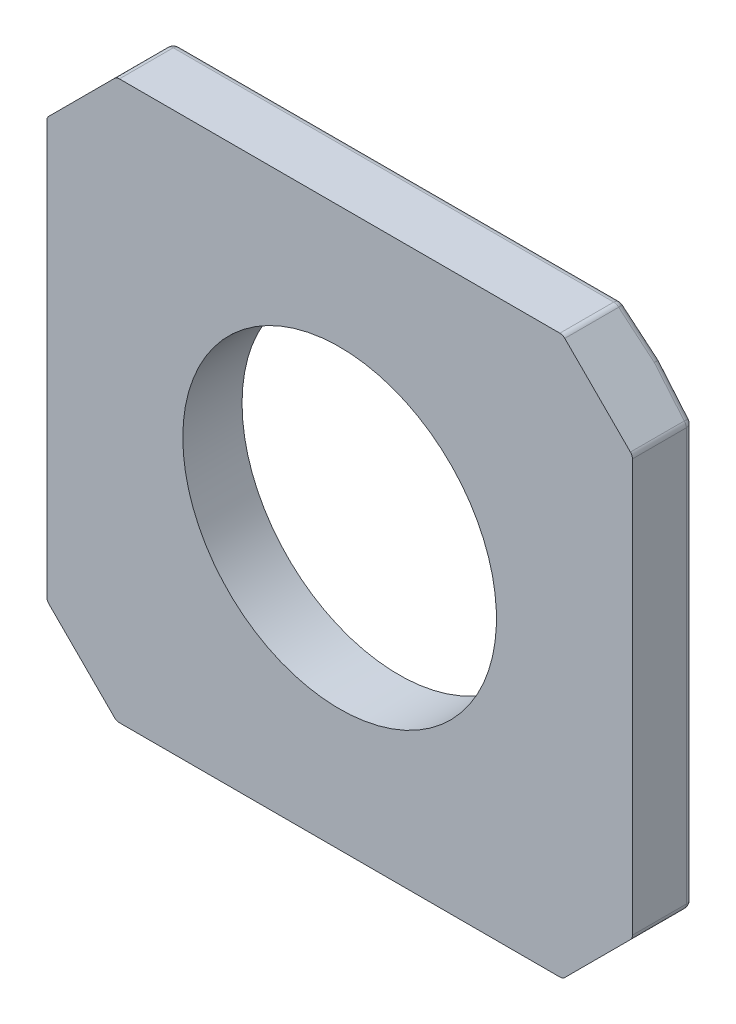
SolidWorks part; units mm, degrees
ref_plane "Top plane" through (0, 0, 0) normal (0, 0, 1) x (1, 0, 0)
ref_plane "Right plane" through (0, 0, 0) normal (0, 1, 0) x (1, 0, 0)
ref_plane "Front plane" through (0, 0, 0) normal (1, 0, 0) x (0, 0, -1)
sketch "Sketch1" plane through (0, 0, 0) normal (0, 0, 1) x (1, 0, 0)
  line L1 (-84.021, 80) -> (84.021, 80)
  line L2 (-84.021, 80) -> (-84.021, -80)
  line L3 (-84.021, -80) -> (84.021, -80)
  line L4 (84.021, 80) -> (84.021, -80)
  line L5 (-84.021, 80) -> (84.021, -80) construction
  line L6 (-60.2161, 15.1309) -> (-64.6493, 12.445)
  line L7 (-64.6493, -12.445) -> (-60.2161, -15.1309)
  line L8 (17.0043, -59.7141) -> (21.5469, -62.2104)
  line L9 (43.1024, -49.7654) -> (43.2118, -44.5833)
  line L10 (43.2118, 44.5833) -> (43.1024, 49.7654)
  line L11 (21.5469, 62.2104) -> (17.0043, 59.7141)
  line L18 (-84.021, -80) -> (84.021, 80) construction
  arc A18 (13.5845, 59.2373) -> (-58.0933, 17.8542) centre (0, 0) ccw
  arc A19 (-60.2161, 15.1309) -> (-58.0933, 17.8542) centre (-62.7293, 19.279) ccw
  arc A20 (-64.6493, 12.445) -> (-67.0879, 8.7029) centre (-61.9807, 8.0404) ccw
  arc A21 (-67.0879, 8.7029) -> (-67.0879, -8.7029) centre (0, 0) ccw
  arc A22 (-67.0879, -8.7029) -> (-64.6493, -12.445) centre (-61.9807, -8.0404) ccw
  arc A23 (-58.0933, -17.8542) -> (-60.2161, -15.1309) centre (-62.7293, -19.279) ccw
  arc A24 (-58.0933, -17.8542) -> (13.5845, -59.2373) centre (0, 0) ccw
  arc A25 (17.0043, -59.7141) -> (13.5845, -59.2373) centre (14.6686, -63.9646) ccw
  arc A26 (21.5469, -62.2104) -> (26.007, -62.4512) centre (24.0272, -57.697) ccw
  arc A27 (26.007, -62.4512) -> (41.0809, -53.7483) centre (0, 0) ccw
  arc A28 (41.0809, -53.7483) -> (43.1024, -49.7654) centre (37.9535, -49.6566) ccw
  arc A29 (44.5088, -41.3832) -> (43.2118, -44.5833) centre (48.0607, -44.6857) ccw
  arc A30 (44.5088, -41.3832) -> (44.5088, 41.3832) centre (0, 0) ccw
  arc A31 (43.2118, 44.5833) -> (44.5088, 41.3832) centre (48.0607, 44.6857) ccw
  arc A32 (43.1024, 49.7654) -> (41.0809, 53.7483) centre (37.9535, 49.6566) ccw
  arc A33 (41.0809, 53.7483) -> (26.007, 62.4512) centre (0, 0) ccw
  arc A34 (26.007, 62.4512) -> (21.5469, 62.2104) centre (24.0272, 57.697) ccw
  arc A35 (13.5845, 59.2373) -> (17.0043, 59.7141) centre (14.6686, 63.9646) ccw
  dimension "D2" = 60.775
  dimension "D3" = 4.85
  dimension "D4" = 160
  dimension "D5" = 60.775
  dimension "D6" = 67.65
  dimension "D1" = 90
  dimension "D7" = 17.4058
extrude "Boss-Extrude1" add sketch "Sketch1" against normal blind 3 contours L4 L1 L2 L3 A18 A35 L11 A34 A33 A32 L10 A31 A30 A29 L9 A28 A27 A26 L8 A25 A24 A23 L7 A22 A21 A20 L6 A19 region at (0, 77.6797, 0)
sketch "Sketch3" plane through (0, 0, 0) normal (0, 0, 1) x (1, 0, 0)
  line L4 (84.021, -80) -> (84.021, 80)
  line L5 (84.021, 80) -> (-84.021, 80)
  line L6 (-84.021, 80) -> (-84.021, -80)
  line L7 (-84.021, -80) -> (84.021, -80)
  line L8 (84.021, -80) -> (84.021, 80)
  line L9 (84.021, 80) -> (-84.021, 80)
  line L10 (-84.021, 80) -> (-84.021, -80)
  line L11 (-84.021, -80) -> (84.021, -80)
  line L12 (84.021, 80) -> (-84.021, 80)
  line L13 (84.021, -80) -> (84.021, 80)
  line L14 (-84.021, -80) -> (84.021, -80)
  line L15 (-84.021, 80) -> (-84.021, -80)
  line L16 (84.021, 80) -> (-84.021, 80)
  line L17 (84.021, -80) -> (84.021, 80)
  line L18 (-84.021, -80) -> (84.021, -80)
  line L19 (-84.021, 80) -> (-84.021, -80)
  line L22 (21.5469, 62.2104) -> (17.0043, 59.7141)
  line L23 (-60.2161, 15.1309) -> (-64.6493, 12.445)
  line L24 (-64.6493, -12.445) -> (-60.2161, -15.1309)
  line L25 (17.0043, -59.7141) -> (21.5469, -62.2104)
  line L26 (43.1024, -49.7654) -> (43.2118, -44.5833)
  line L27 (43.2118, 44.5833) -> (43.1024, 49.7654)
  line L28 (21.5469, 62.2104) -> (17.0043, 59.7141)
  line L29 (-60.2161, 15.1309) -> (-64.6493, 12.445)
  line L30 (-64.6493, -12.445) -> (-60.2161, -15.1309)
  line L31 (17.0043, -59.7141) -> (21.5469, -62.2104)
  line L32 (43.1024, -49.7654) -> (43.2118, -44.5833)
  line L33 (43.2118, 44.5833) -> (43.1024, 49.7654)
  circle A0 centre (0, 0) radius 45
  arc A18 (13.5845, 59.2373) -> (17.0043, 59.7141) centre (14.6686, 63.9646) ccw
  arc A19 (13.5845, 59.2373) -> (-58.0933, 17.8542) centre (0, 0) ccw
  arc A20 (-60.2161, 15.1309) -> (-58.0933, 17.8542) centre (-62.7293, 19.279) ccw
  arc A21 (-64.6493, 12.445) -> (-67.0879, 8.7029) centre (-61.9807, 8.0404) ccw
  arc A22 (-67.0879, 8.7029) -> (-67.0879, -8.7029) centre (0, 0) ccw
  arc A23 (-67.0879, -8.7029) -> (-64.6493, -12.445) centre (-61.9807, -8.0404) ccw
  arc A24 (-58.0933, -17.8542) -> (-60.2161, -15.1309) centre (-62.7293, -19.279) ccw
  arc A25 (-58.0933, -17.8542) -> (13.5845, -59.2373) centre (0, 0) ccw
  arc A26 (17.0043, -59.7141) -> (13.5845, -59.2373) centre (14.6686, -63.9646) ccw
  arc A27 (21.5469, -62.2104) -> (26.007, -62.4512) centre (24.0272, -57.697) ccw
  arc A28 (26.007, -62.4512) -> (41.0809, -53.7483) centre (0, 0) ccw
  arc A29 (41.0809, -53.7483) -> (43.1024, -49.7654) centre (37.9535, -49.6566) ccw
  arc A30 (44.5088, -41.3832) -> (43.2118, -44.5833) centre (48.0607, -44.6857) ccw
  arc A31 (44.5088, -41.3832) -> (44.5088, 41.3832) centre (0, 0) ccw
  arc A32 (43.2118, 44.5833) -> (44.5088, 41.3832) centre (48.0607, 44.6857) ccw
  arc A33 (43.1024, 49.7654) -> (41.0809, 53.7483) centre (37.9535, 49.6566) ccw
  arc A34 (41.0809, 53.7483) -> (26.007, 62.4512) centre (0, 0) ccw
  arc A35 (26.007, 62.4512) -> (21.5469, 62.2104) centre (24.0272, 57.697) ccw
  arc A36 (13.5845, 59.2373) -> (17.0043, 59.7141) centre (14.6686, 63.9646) ccw
  arc A37 (13.5845, 59.2373) -> (-58.0933, 17.8542) centre (0, 0) ccw
  arc A38 (-60.2161, 15.1309) -> (-58.0933, 17.8542) centre (-62.7293, 19.279) ccw
  arc A39 (-64.6493, 12.445) -> (-67.0879, 8.7029) centre (-61.9807, 8.0404) ccw
  arc A40 (-67.0879, 8.7029) -> (-67.0879, -8.7029) centre (0, 0) ccw
  arc A41 (-67.0879, -8.7029) -> (-64.6493, -12.445) centre (-61.9807, -8.0404) ccw
  arc A42 (-58.0933, -17.8542) -> (-60.2161, -15.1309) centre (-62.7293, -19.279) ccw
  arc A43 (-58.0933, -17.8542) -> (13.5845, -59.2373) centre (0, 0) ccw
  arc A44 (17.0043, -59.7141) -> (13.5845, -59.2373) centre (14.6686, -63.9646) ccw
  arc A45 (21.5469, -62.2104) -> (26.007, -62.4512) centre (24.0272, -57.697) ccw
  arc A46 (26.007, -62.4512) -> (41.0809, -53.7483) centre (0, 0) ccw
  arc A47 (41.0809, -53.7483) -> (43.1024, -49.7654) centre (37.9535, -49.6566) ccw
  arc A48 (44.5088, -41.3832) -> (43.2118, -44.5833) centre (48.0607, -44.6857) ccw
  arc A49 (44.5088, -41.3832) -> (44.5088, 41.3832) centre (0, 0) ccw
  arc A50 (43.2118, 44.5833) -> (44.5088, 41.3832) centre (48.0607, 44.6857) ccw
  arc A51 (43.1024, 49.7654) -> (41.0809, 53.7483) centre (37.9535, 49.6566) ccw
  arc A52 (41.0809, 53.7483) -> (26.007, 62.4512) centre (0, 0) ccw
  arc A53 (26.007, 62.4512) -> (21.5469, 62.2104) centre (24.0272, 57.697) ccw
  arc M37 (-58.0933, 17.8542) -> (13.5845, 59.2373) centre (0, 0) cw
  arc M38 (13.5845, 59.2373) -> (17.0043, 59.7141) centre (14.6686, 63.9646) ccw
  line M39 (17.0043, 59.7141) -> (21.5469, 62.2104)
  arc M40 (21.5469, 62.2104) -> (26.007, 62.4512) centre (24.0272, 57.697) cw
  arc M41 (26.007, 62.4512) -> (41.0809, 53.7483) centre (0, 0) cw
  arc M42 (41.0809, 53.7483) -> (43.1024, 49.7654) centre (37.9535, 49.6566) cw
  line M43 (43.1024, 49.7654) -> (43.2118, 44.5833)
  arc M44 (43.2118, 44.5833) -> (44.5088, 41.3832) centre (48.0607, 44.6857) ccw
  arc M45 (44.5088, 41.3832) -> (44.5088, -41.3832) centre (0, 0) cw
  arc M46 (44.5088, -41.3832) -> (43.2118, -44.5833) centre (48.0607, -44.6857) ccw
  line M47 (43.2118, -44.5833) -> (43.1024, -49.7654)
  arc M48 (43.1024, -49.7654) -> (41.0809, -53.7483) centre (37.9535, -49.6566) cw
  arc M49 (41.0809, -53.7483) -> (26.007, -62.4512) centre (0, 0) cw
  arc M50 (26.007, -62.4512) -> (21.5469, -62.2104) centre (24.0272, -57.697) cw
  line M51 (21.5469, -62.2104) -> (17.0043, -59.7141)
  arc M52 (17.0043, -59.7141) -> (13.5845, -59.2373) centre (14.6686, -63.9646) ccw
  arc M53 (13.5845, -59.2373) -> (-58.0933, -17.8542) centre (0, 0) cw
  arc M54 (-58.0933, -17.8542) -> (-60.2161, -15.1309) centre (-62.7293, -19.279) ccw
  line M55 (-60.2161, -15.1309) -> (-64.6493, -12.445)
  arc M56 (-64.6493, -12.445) -> (-67.0879, -8.7029) centre (-61.9807, -8.0404) cw
  arc M57 (-67.0879, -8.7029) -> (-67.0879, 8.7029) centre (0, 0) cw
  arc M58 (-67.0879, 8.7029) -> (-64.6493, 12.445) centre (-61.9807, 8.0404) cw
  line M59 (-64.6493, 12.445) -> (-60.2161, 15.1309)
  arc M60 (-60.2161, 15.1309) -> (-58.0933, 17.8542) centre (-62.7293, 19.279) ccw
  dimension "D1" = 0
  dimension "D2" = 0
  dimension "D3" = 0
extrude "Boss-Extrude4" add sketch "Sketch3" along normal blind 5 separate body contours A0 M37 M60 M59 M58 M57 M56 M55 M54 M53 M52 M51 M50 M49 M48 M47 M46 M45 M44 M43 M42 M41 M40 M39 M38 region at (23.8464, 61.0451, 0)
chamfer "Chamfer1" distance 31 angle 5 4 edges at (0, 80, -3) (84.021, 0, -3) (0, -80, -3) (-84.021, 0, -3) first distance on face at (0, 0, -3)
sketch "Sketch4" plane through (0, 0, -4) normal (0, 0, -1) x (-1, 0, 0)
  circle A0 centre (42, 35) radius 1.7
  circle A1 centre (42, -35) radius 1.7
  circle A2 centre (-42, -35) radius 1.6836
  circle A3 centre (-42, 35) radius 1.7
extrude "Cut-Extrude1" cut sketch "Sketch4" against normal blind 52
sketch "Sketch5" plane through (0, 0, 0) normal (0, 0, 1) x (1, 0, 0)
  line L4 (84.021, -80) -> (84.021, 80)
  line L5 (84.021, 80) -> (-84.021, 80)
  line L6 (-84.021, 80) -> (-84.021, -80)
  line L7 (-84.021, -80) -> (84.021, -80)
  line L8 (84.021, -80) -> (84.021, 80)
  line L9 (84.021, 80) -> (-84.021, 80)
  line L10 (-84.021, 80) -> (-84.021, -80)
  line L11 (-84.021, -80) -> (84.021, -80)
  line L12 (84.021, 80) -> (-84.021, 80)
  line L13 (84.021, -80) -> (84.021, 80)
  line L14 (-84.021, -80) -> (84.021, -80)
  line L15 (-84.021, 80) -> (-84.021, -80)
  line L16 (84.021, 80) -> (-84.021, 80)
  line L17 (84.021, -80) -> (84.021, 80)
  line L18 (-84.021, -80) -> (84.021, -80)
  line L19 (-84.021, 80) -> (-84.021, -80)
  line L22 (21.5469, 62.2104) -> (17.0043, 59.7141)
  line L23 (-60.2161, 15.1309) -> (-64.6493, 12.445)
  line L24 (-64.6493, -12.445) -> (-60.2161, -15.1309)
  line L25 (17.0043, -59.7141) -> (21.5469, -62.2104)
  line L26 (43.1024, -49.7654) -> (43.2118, -44.5833)
  line L27 (43.2118, 44.5833) -> (43.1024, 49.7654)
  line L28 (21.5469, 62.2104) -> (17.0043, 59.7141)
  line L29 (-60.2161, 15.1309) -> (-64.6493, 12.445)
  line L30 (-64.6493, -12.445) -> (-60.2161, -15.1309)
  line L31 (17.0043, -59.7141) -> (21.5469, -62.2104)
  line L32 (43.1024, -49.7654) -> (43.2118, -44.5833)
  line L33 (43.2118, 44.5833) -> (43.1024, 49.7654)
  circle A0 centre (0, 0) radius 45 construction
  circle A1 centre (0, 0) radius 45
  arc A18 (13.5845, 59.2373) -> (17.0043, 59.7141) centre (14.6686, 63.9646) ccw
  arc A19 (13.5845, 59.2373) -> (-58.0933, 17.8542) centre (0, 0) ccw
  arc A20 (-60.2161, 15.1309) -> (-58.0933, 17.8542) centre (-62.7293, 19.279) ccw
  arc A21 (-64.6493, 12.445) -> (-67.0879, 8.7029) centre (-61.9807, 8.0404) ccw
  arc A22 (-67.0879, 8.7029) -> (-67.0879, -8.7029) centre (0, 0) ccw
  arc A23 (-67.0879, -8.7029) -> (-64.6493, -12.445) centre (-61.9807, -8.0404) ccw
  arc A24 (-58.0933, -17.8542) -> (-60.2161, -15.1309) centre (-62.7293, -19.279) ccw
  arc A25 (-58.0933, -17.8542) -> (13.5845, -59.2373) centre (0, 0) ccw
  arc A26 (17.0043, -59.7141) -> (13.5845, -59.2373) centre (14.6686, -63.9646) ccw
  arc A27 (21.5469, -62.2104) -> (26.007, -62.4512) centre (24.0272, -57.697) ccw
  arc A28 (26.007, -62.4512) -> (41.0809, -53.7483) centre (0, 0) ccw
  arc A29 (41.0809, -53.7483) -> (43.1024, -49.7654) centre (37.9535, -49.6566) ccw
  arc A30 (44.5088, -41.3832) -> (43.2118, -44.5833) centre (48.0607, -44.6857) ccw
  arc A31 (44.5088, -41.3832) -> (44.5088, 41.3832) centre (0, 0) ccw
  arc A32 (43.2118, 44.5833) -> (44.5088, 41.3832) centre (48.0607, 44.6857) ccw
  arc A33 (43.1024, 49.7654) -> (41.0809, 53.7483) centre (37.9535, 49.6566) ccw
  arc A34 (41.0809, 53.7483) -> (26.007, 62.4512) centre (0, 0) ccw
  arc A35 (26.007, 62.4512) -> (21.5469, 62.2104) centre (24.0272, 57.697) ccw
  arc A36 (13.5845, 59.2373) -> (17.0043, 59.7141) centre (14.6686, 63.9646) ccw
  arc A37 (13.5845, 59.2373) -> (-58.0933, 17.8542) centre (0, 0) ccw
  arc A38 (-60.2161, 15.1309) -> (-58.0933, 17.8542) centre (-62.7293, 19.279) ccw
  arc A39 (-64.6493, 12.445) -> (-67.0879, 8.7029) centre (-61.9807, 8.0404) ccw
  arc A40 (-67.0879, 8.7029) -> (-67.0879, -8.7029) centre (0, 0) ccw
  arc A41 (-67.0879, -8.7029) -> (-64.6493, -12.445) centre (-61.9807, -8.0404) ccw
  arc A42 (-58.0933, -17.8542) -> (-60.2161, -15.1309) centre (-62.7293, -19.279) ccw
  arc A43 (-58.0933, -17.8542) -> (13.5845, -59.2373) centre (0, 0) ccw
  arc A44 (17.0043, -59.7141) -> (13.5845, -59.2373) centre (14.6686, -63.9646) ccw
  arc A45 (21.5469, -62.2104) -> (26.007, -62.4512) centre (24.0272, -57.697) ccw
  arc A46 (26.007, -62.4512) -> (41.0809, -53.7483) centre (0, 0) ccw
  arc A47 (41.0809, -53.7483) -> (43.1024, -49.7654) centre (37.9535, -49.6566) ccw
  arc A48 (44.5088, -41.3832) -> (43.2118, -44.5833) centre (48.0607, -44.6857) ccw
  arc A49 (44.5088, -41.3832) -> (44.5088, 41.3832) centre (0, 0) ccw
  arc A50 (43.2118, 44.5833) -> (44.5088, 41.3832) centre (48.0607, 44.6857) ccw
  arc A51 (43.1024, 49.7654) -> (41.0809, 53.7483) centre (37.9535, 49.6566) ccw
  arc A52 (41.0809, 53.7483) -> (26.007, 62.4512) centre (0, 0) ccw
  arc A53 (26.007, 62.4512) -> (21.5469, 62.2104) centre (24.0272, 57.697) ccw
  line M33 (84.021, -80) -> (84.021, 80)
  line M34 (84.021, 80) -> (-84.021, 80)
  line M35 (-84.021, 80) -> (-84.021, -80)
  line M36 (-84.021, -80) -> (84.021, -80)
  arc M37 (-58.0933, 17.8542) -> (13.5845, 59.2373) centre (0, 0) cw
  arc M38 (13.5845, 59.2373) -> (17.0043, 59.7141) centre (14.6686, 63.9646) ccw
  line M39 (17.0043, 59.7141) -> (21.5469, 62.2104)
  arc M40 (21.5469, 62.2104) -> (26.007, 62.4512) centre (24.0272, 57.697) cw
  arc M41 (26.007, 62.4512) -> (41.0809, 53.7483) centre (0, 0) cw
  arc M42 (41.0809, 53.7483) -> (43.1024, 49.7654) centre (37.9535, 49.6566) cw
  line M43 (43.1024, 49.7654) -> (43.2118, 44.5833)
  arc M44 (43.2118, 44.5833) -> (44.5088, 41.3832) centre (48.0607, 44.6857) ccw
  arc M45 (44.5088, 41.3832) -> (44.5088, -41.3832) centre (0, 0) cw
  arc M46 (44.5088, -41.3832) -> (43.2118, -44.5833) centre (48.0607, -44.6857) ccw
  line M47 (43.2118, -44.5833) -> (43.1024, -49.7654)
  arc M48 (43.1024, -49.7654) -> (41.0809, -53.7483) centre (37.9535, -49.6566) cw
  arc M49 (41.0809, -53.7483) -> (26.007, -62.4512) centre (0, 0) cw
  arc M50 (26.007, -62.4512) -> (21.5469, -62.2104) centre (24.0272, -57.697) cw
  line M51 (21.5469, -62.2104) -> (17.0043, -59.7141)
  arc M52 (17.0043, -59.7141) -> (13.5845, -59.2373) centre (14.6686, -63.9646) ccw
  arc M53 (13.5845, -59.2373) -> (-58.0933, -17.8542) centre (0, 0) cw
  arc M54 (-58.0933, -17.8542) -> (-60.2161, -15.1309) centre (-62.7293, -19.279) ccw
  line M55 (-60.2161, -15.1309) -> (-64.6493, -12.445)
  arc M56 (-64.6493, -12.445) -> (-67.0879, -8.7029) centre (-61.9807, -8.0404) cw
  arc M57 (-67.0879, -8.7029) -> (-67.0879, 8.7029) centre (0, 0) cw
  arc M58 (-67.0879, 8.7029) -> (-64.6493, 12.445) centre (-61.9807, 8.0404) cw
  line M59 (-64.6493, 12.445) -> (-60.2161, 15.1309)
  arc M60 (-60.2161, 15.1309) -> (-58.0933, 17.8542) centre (-62.7293, 19.279) ccw
  dimension "D1" = 0
  dimension "D2" = 0
  dimension "D3" = 0
extrude "Boss-Extrude5" add sketch "Sketch5" along normal blind 30 contours M36 M33 M34 M35 M60 M37 M38 M39 M40 M41 M42 M43 M44 M45 M46 M47 M48 M49 M50 M51 M52 M53 M54 M55 M56 M57 M58 M59 | A1 M37 M60 M59 M58 M57 M56 M55 M54 M53 M52 M51 M50 M49 M48 M47 M46 M45 M44 M43 M42 M41 M40 M39 M38 region at (0, -77.6797, 0) region at (23.8464, 61.0451, 0)
chamfer "Chamfer2" distance 20 angle 45 4 edges at (-84.021, -80, 14.8561) (-84.021, 80, 14.8561) (84.021, -80, 14.8561) (84.021, 80, 14.8561)
fillet "Fillet1" radius 2 20 edges at (-64.021, 80, 14.8561) (-84.021, 60, 14.8561) (-84.021, -60, 14.8561) (-64.021, -80, 14.8561) (64.021, -80, 14.8561) (84.021, -60, 14.8561) (64.021, 80, 14.8561) (84.021, 60, 14.8561) (-79.021, -65, -0.7253) (-69.021, -75, -0.7253) (0, -80, -0.2879) (69.021, -75, -0.7253) (79.021, -65, -0.7253) (84.021, 0, -0.2879) (79.021, 65, -0.7253) (-79.021, 65, -0.7253) (-84.021, 0, -0.2879) (-69.021, 75, -0.7253) (69.021, 75, -0.7253) (0, 80, -0.2879)
sketch "Sketch6" plane through (-84.021, 0, 0) normal (-1, 0, 0) x (0, 0, 1)
  text T0 "FALCON" font "ROG Fonts" height 4
extrude "Boss-Extrude6" add sketch "Sketch6" along normal blind 2 separate body
move or copy body "Body-Move/Copy1" bodies to move or copy 105 106 107 108 109 110 copy no rotation origin (0, 1.9983, 14.1591) rotation axis (-1, 0, 0) rotation angle 90
sketch "Sketch8" plane through (0, 0, 0) normal (0, 0, -1) x (-1, 0, 0)
  circle A0 centre (42, -35) radius 1.7
  circle A2 centre (42, 35) radius 1.7
  circle A3 centre (-42, -35) radius 1.7
  circle A5 centre (-42, 35) radius 1.7
extrude "Cut-Extrude2" cut sketch "Sketch8" against normal blind 6
sketch3d "3DSketch1"
  line L8 (63.1926, 80, 30) -> (-63.1926, 80, 30)
  line L9 (-64.6068, 79.4142, 30) -> (-83.4352, 60.5858, 30)
  line L10 (-84.021, 59.1716, 30) -> (-84.021, -59.1716, 30)
  line L11 (-83.4352, -60.5858, 30) -> (-64.6068, -79.4142, 30)
  line L12 (-63.1926, -80, 30) -> (63.1926, -80, 30)
  line L13 (64.6068, -79.4142, 30) -> (83.4352, -60.5858, 30)
  line L14 (84.021, -59.1716, 30) -> (84.021, 59.1716, 30)
  line L15 (83.4352, 60.5858, 30) -> (64.6068, 79.4142, 30)
  line L16 (63.1926, 80, 30) -> (-63.1926, 80, 30)
  line L17 (-64.6068, 79.4142, 30) -> (-83.4352, 60.5858, 30)
  line L18 (-84.021, 59.1716, 30) -> (-84.021, -59.1716, 30)
  line L19 (-83.4352, -60.5858, 30) -> (-64.6068, -79.4142, 30)
  line L20 (-63.1926, -80, 30) -> (63.1926, -80, 30)
  line L21 (64.6068, -79.4142, 30) -> (83.4352, -60.5858, 30)
  line L22 (84.021, -59.1716, 30) -> (84.021, 59.1716, 30)
  line L23 (83.4352, 60.5858, 30) -> (64.6068, 79.4142, 30)
  arc A8 (-63.1926, 80, 30) -> (-64.6068, 79.4142, 30) centre (-63.1926, 78, 30) ccw
  arc A9 (-83.4352, 60.5858, 30) -> (-84.021, 59.1716, 30) centre (-82.021, 59.1716, 30) ccw
  arc A10 (-84.021, -59.1716, 30) -> (-83.4352, -60.5858, 30) centre (-82.021, -59.1716, 30) ccw
  arc A11 (-64.6068, -79.4142, 30) -> (-63.1926, -80, 30) centre (-63.1926, -78, 30) ccw
  arc A12 (63.1926, -80, 30) -> (64.6068, -79.4142, 30) centre (63.1926, -78, 30) ccw
  arc A13 (83.4352, -60.5858, 30) -> (84.021, -59.1716, 30) centre (82.021, -59.1716, 30) ccw
  arc A14 (84.021, 59.1716, 30) -> (83.4352, 60.5858, 30) centre (82.021, 59.1716, 30) ccw
  arc A15 (64.6068, 79.4142, 30) -> (63.1926, 80, 30) centre (63.1926, 78, 30) ccw
  arc A16 (-63.1926, 80, 30) -> (-64.6068, 79.4142, 30) centre (-63.1926, 78, 30) ccw
  arc A17 (-83.4352, 60.5858, 30) -> (-84.021, 59.1716, 30) centre (-82.021, 59.1716, 30) ccw
  arc A18 (-84.021, -59.1716, 30) -> (-83.4352, -60.5858, 30) centre (-82.021, -59.1716, 30) ccw
  arc A19 (-64.6068, -79.4142, 30) -> (-63.1926, -80, 30) centre (-63.1926, -78, 30) ccw
  arc A20 (63.1926, -80, 30) -> (64.6068, -79.4142, 30) centre (63.1926, -78, 30) ccw
  arc A21 (83.4352, -60.5858, 30) -> (84.021, -59.1716, 30) centre (82.021, -59.1716, 30) ccw
  arc A22 (84.021, 59.1716, 30) -> (83.4352, 60.5858, 30) centre (82.021, 59.1716, 30) ccw
  arc A23 (64.6068, 79.4142, 30) -> (63.1926, 80, 30) centre (63.1926, 78, 30) ccw
  point P6 (-63.1926, 78, 32)
  point P12 (-82.021, 59.1716, 32)
  point P18 (-82.021, -59.1716, 32)
  point P24 (-63.1926, -78, 32)
  point P30 (63.1926, -78, 32)
  point P36 (82.021, -59.1716, 32)
  point P42 (82.021, 59.1716, 32)
  point P46 (63.1926, 78, 32)
  point P48 (-63.1926, 78, 32)
  point P49 (-82.021, 59.1716, 32)
  point P50 (-82.021, -59.1716, 32)
  point P51 (-63.1926, -78, 32)
  point P52 (63.1926, -78, 32)
  point P53 (82.021, -59.1716, 32)
  point P54 (82.021, 59.1716, 32)
  point P55 (63.1926, 78, 32)
  dimension "D1" = 0
extrude "Cut-Extrude3" cut sketch "3DSketch1" along a picked direction on the side against the normal blind 13
move or copy body "Body-Move/Copy2" bodies to move or copy 112 113 114 115 116 111 copy no translate (0, 0, -4.5639) parameters "D1"=0, "D2"=0, "D3"=4.5639
